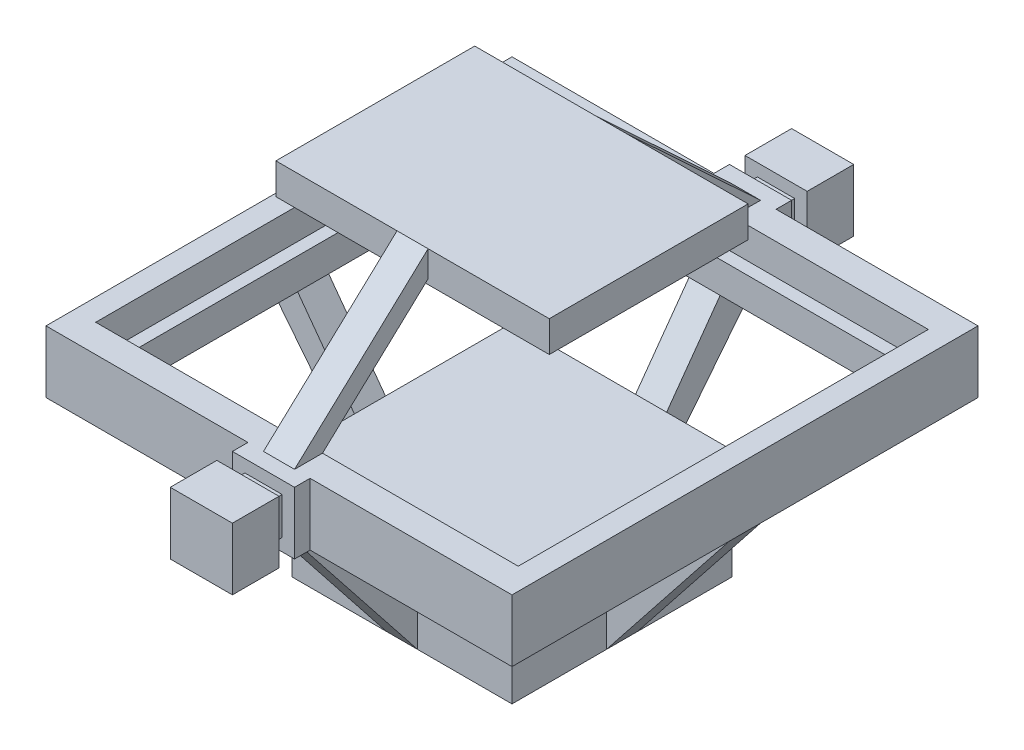
SolidWorks part; units mm, degrees
ref_plane "Front Plane" through (0, 0, 0) normal (0, 0, 1) x (1, 0, 0)
ref_plane "Top Plane" through (0, 0, 0) normal (0, 1, 0) x (1, 0, 0)
ref_plane "Right Plane" through (0, 0, 0) normal (1, 0, 0) x (0, 0, -1)
sketch "Sketch2" plane through (0, 0, 0) normal (0, 1, 0) x (1, 0, 0)
  line L1 (-37.5, 37.5) -> (37.5, 37.5)
  line L2 (-37.5, 37.5) -> (-37.5, -37.5)
  line L3 (-37.5, -37.5) -> (37.5, -37.5)
  line L4 (37.5, 37.5) -> (37.5, -37.5)
  line L5 (-37.5, 37.5) -> (37.5, -37.5) construction
  line L6 (-37.5, -37.5) -> (37.5, 37.5) construction
  point P0 (0, 0)
  point P6 (0, 0)
extrude "Boss-Extrude1" add sketch "Sketch2" along normal blind 5
extrude "Boss-Extrude2" add sketch "Sketch2<2>" against normal blind 5
sketch "Sketch2<2>" plane through (0, 0, 0) normal (0, 1, 0) x (1, 0, 0) same geometry as "Sketch2"
sketch "Sketch4" plane through (0, 5, 0) normal (0, 1, 0) x (1, 0, 0)
  line L1 (-34, 33) -> (34, 33)
  line L2 (-34, 33) -> (-34, -33)
  line L3 (-34, -33) -> (34, -33)
  line L4 (34, 33) -> (34, -33)
  line L5 (-34, 33) -> (34, -33) construction
  line L6 (-34, -33) -> (34, 33) construction
  point P0 (0, 0)
extrude "Cut-Extrude1" cut sketch "Sketch4" against normal blind 5
sketch "Sketch5" plane through (0, 0, 0) normal (0, 1, 0) x (1, 0, 0)
  line L1 (-32, 31) -> (32, 31)
  line L2 (-32, 31) -> (-32, -31)
  line L3 (-32, -31) -> (32, -31)
  line L4 (32, 31) -> (32, -31)
  line L5 (-32, 31) -> (32, -31) construction
  line L6 (-32, -31) -> (32, 31) construction
  point P0 (0, 0)
extrude "Cut-Extrude2" cut sketch "Sketch5" against normal blind 5
sketch "Sketch6" plane through (0, 0, 37.5) normal (0, 0, 1) x (1, 0, 0)
  line L0 (-37.5, -5) -> (37.5, -5) construction
  line L1 (-5, 5) -> (5, 5)
  line L2 (-5, 5) -> (-5, -5)
  line L3 (-5, -5) -> (5, -5)
  line L4 (5, 5) -> (5, -5)
  line L5 (-5, 5) -> (5, -5) construction
  line L6 (-5, -5) -> (5, 5) construction
  point P0 (0, 0)
  point P8 (0, 0)
extrude "Boss-Extrude3" add sketch "Sketch6" along normal blind 2.5
sketch "Sketch7" plane through (0, 0, 40) normal (0, 0, 1) x (1, 0, 0)
  line L1 (-3, 3) -> (3, 3)
  line L2 (-3, 3) -> (-3, -3)
  line L3 (-3, -3) -> (3, -3)
  line L4 (3, 3) -> (3, -3)
  line L5 (-3, 3) -> (3, -3) construction
  line L6 (-3, -3) -> (3, 3) construction
  point P0 (0, 0)
  point P6 (0, 0)
extrude "Boss-Extrude4" add sketch "Sketch7" along normal blind 2.5
sketch "Sketch8" plane through (0, 0, 42.5) normal (0, 0, 1) x (1, 0, 0)
  line L1 (-5, 5) -> (5, 5)
  line L2 (-5, 5) -> (-5, -5)
  line L3 (-5, -5) -> (5, -5)
  line L4 (5, 5) -> (5, -5)
  line L5 (-5, 5) -> (5, -5) construction
  line L6 (-5, -5) -> (5, 5) construction
  point P0 (0, 0)
extrude "Boss-Extrude5" add sketch "Sketch8" along normal blind 7.5
sketch "Sketch9" plane through (0, 0, -37.5) normal (0, 0, -1) x (-1, 0, 0)
  line L1 (-5, 5) -> (5, 5)
  line L2 (-5, 5) -> (-5, -5)
  line L3 (-5, -5) -> (5, -5)
  line L4 (5, 5) -> (5, -5)
  line L5 (-5, 5) -> (5, -5) construction
  line L6 (-5, -5) -> (5, 5) construction
  point P0 (0, 0)
extrude "Boss-Extrude6" add sketch "Sketch9" along normal blind 2.5
sketch "Sketch10" plane through (0, 0, -40) normal (0, 0, -1) x (-1, 0, 0)
  line L1 (-3, 3) -> (3, 3)
  line L2 (-3, 3) -> (-3, -3)
  line L3 (-3, -3) -> (3, -3)
  line L4 (3, 3) -> (3, -3)
  line L5 (-3, 3) -> (3, -3) construction
  line L6 (-3, -3) -> (3, 3) construction
  point P0 (0, 0)
extrude "Boss-Extrude7" add sketch "Sketch10" along normal blind 2.5
sketch "Sketch11" plane through (0, 0, -42.5) normal (0, 0, -1) x (-1, 0, 0)
  line L1 (-5, 5) -> (5, 5)
  line L2 (-5, 5) -> (-5, -5)
  line L3 (-5, -5) -> (5, -5)
  line L4 (5, 5) -> (5, -5)
  line L5 (-5, 5) -> (5, -5) construction
  line L6 (-5, -5) -> (5, 5) construction
  point P0 (0, 0)
extrude "Boss-Extrude8" add sketch "Sketch11" along normal blind 7.5
ref_plane "Plane3" through (0, 30, 0) normal (0, 1, 0) x (1, 0, 0)
ref_plane "Plane4" through (0, 25, 0) normal (0, 1, 0) x (1, 0, 0)
ref_plane "Plane5" through (0, -30, 0) normal (0, 1, 0) x (1, 0, 0)
sketch "Sketch12" plane through (0, -30, 0) normal (0, 1, 0) x (1, 0, 0)
  line L1 (-17.7, 17.7) -> (17.7, 17.7)
  line L2 (-17.7, 17.7) -> (-17.7, -17.7)
  line L3 (-17.7, -17.7) -> (17.7, -17.7)
  line L4 (17.7, 17.7) -> (17.7, -17.7)
  line L5 (-17.7, 17.7) -> (17.7, -17.7) construction
  line L6 (-17.7, -17.7) -> (17.7, 17.7) construction
  point P0 (0, 0)
extrude "Boss-Extrude9" add sketch "Sketch12" along normal blind 17.7 separate body
sketch "Sketch13" plane through (0, -30, 0) normal (0, -1, 0) x (1, 0, 0)
  line L1 (-12.7, 12.7) -> (12.7, 12.7)
  line L2 (-12.7, 12.7) -> (-12.7, -12.7)
  line L3 (-12.7, -12.7) -> (12.7, -12.7)
  line L4 (12.7, 12.7) -> (12.7, -12.7)
  line L5 (-12.7, 12.7) -> (12.7, -12.7) construction
  line L6 (-12.7, -12.7) -> (12.7, 12.7) construction
  point P0 (0, 0)
extrude "Cut-Extrude3" cut sketch "Sketch13" against normal blind 12.7
sketch "Sketch14" plane through (0, 25, 0) normal (0, 1, 0) x (1, 0, 0)
  line L1 (-22, 16) -> (22, 16)
  line L2 (-22, 16) -> (-22, -16)
  line L3 (-22, -16) -> (22, -16)
  line L4 (22, 16) -> (22, -16)
  line L5 (-22, 16) -> (22, -16) construction
  line L6 (-22, -16) -> (22, 16) construction
  point P0 (0, 0)
extrude "Boss-Extrude10" add sketch "Sketch14" against normal blind 5 separate body
sketch "Sketch15" plane through (0, 0, 0) normal (0, 0, 1) x (1, 0, 0)
  line L0 (17.7, -30) -> (37.5, -5)
  line L1 (41.25, -30) -> (-41.25, -30) construction
  line L2 (17.7, -12.3) -> (17.7, -30) construction
  line L3 (37.5, -5) -> (32, -5)
  line L4 (17.7, -30) -> (17.7, -24.5)
  line L5 (32, -5) -> (17.7, -24.5)
extrude "Boss-Extrude11" add sketch "Sketch15" along normal blind 2.5
extrude "Boss-Extrude12" add sketch "Sketch15<2>" against normal blind 2.5
sketch "Sketch15<2>" plane through (0, 0, 0) normal (0, 0, 1) x (1, 0, 0) same geometry as "Sketch15"
sketch "Sketch17" plane through (0, 0, 0) normal (0, 0, 1) x (1, 0, 0)
  line L0 (-37.5, -5) -> (-17.7, -30)
  line L1 (41.25, -30) -> (-41.25, -30) construction
  line L2 (-17.7, -12.3) -> (-17.7, -30) construction
  line L3 (-17.7, -30) -> (-17.7, -24.5)
  line L4 (-37.5, -5) -> (-32, -5)
  line L5 (-32, -5) -> (-17.7, -24.5)
extrude "Boss-Extrude13" add sketch "Sketch17" along normal blind 2.5
extrude "Boss-Extrude14" add sketch "Sketch17<2>" against normal blind 2.5
sketch "Sketch17<2>" plane through (0, 0, 0) normal (0, 0, 1) x (1, 0, 0) same geometry as "Sketch17"
sketch "Sketch18" plane through (0, 0, 0) normal (1, 0, 0) x (0, 0, -1)
  line L0 (16, 25) -> (37.5, 5)
  line L1 (41.25, 25) -> (-41.25, 25) construction
  line L2 (16, 20) -> (16, 25) construction
  line L3 (37.5, 5) -> (33, 5)
  line L4 (33, 5) -> (16, 20.814)
  line L5 (16, 20.814) -> (16, 25)
extrude "Boss-Extrude15" add sketch "Sketch18" along normal blind 2.5
extrude "Boss-Extrude16" add sketch "Sketch18<2>" against normal blind 2.5
sketch "Sketch18<2>" plane through (0, 0, 0) normal (1, 0, 0) x (0, 0, -1) same geometry as "Sketch18"
sketch "Sketch19" plane through (0, 0, 0) normal (1, 0, 0) x (0, 0, -1)
  line L0 (-16, 25) -> (-37.5, 5)
  line L1 (41.25, 25) -> (-41.25, 25) construction
  line L2 (-16, 20) -> (-16, 25) construction
  line L3 (-37.5, 5) -> (-33, 5)
  line L4 (-33, 5) -> (-16, 20.814)
  line L5 (-16, 20.814) -> (-16, 25)
extrude "Boss-Extrude17" add sketch "Sketch19" along normal blind 2.5
extrude "Boss-Extrude18" add sketch "Sketch19<2>" against normal blind 2.5
sketch "Sketch19<2>" plane through (0, 0, 0) normal (1, 0, 0) x (0, 0, -1) same geometry as "Sketch19"
sketch "Sketch20" plane through (0, 0, 0) normal (1, 0, 0) x (0, 0, -1)
  line L0 (-37.5, -5) -> (-17.7, -30)
  line L1 (41.25, -30) -> (-41.25, -30) construction
  line L2 (-17.7, -12.3) -> (-17.7, -30) construction
  line L7 (17.7, -30) -> (37.5, -5)
  line L8 (17.7, -12.3) -> (17.7, -30) construction
  line L9 (37.5, -5) -> (31, -5)
  line L10 (-37.5, -5) -> (-31, -5)
  line L11 (-17.7, -30) -> (-17.7, -23.5)
  line L12 (-31, -5) -> (-17.7, -23.5)
  line L13 (17.7, -30) -> (17.7, -23.5)
  line L14 (31, -5) -> (17.7, -23.5)
extrude "Boss-Extrude19" add sketch "Sketch20" along normal blind 2.5
extrude "Boss-Extrude20" add sketch "Sketch20<2>" against normal blind 2.5
sketch "Sketch20<2>" plane through (0, 0, 0) normal (1, 0, 0) x (0, 0, -1) same geometry as "Sketch20"
